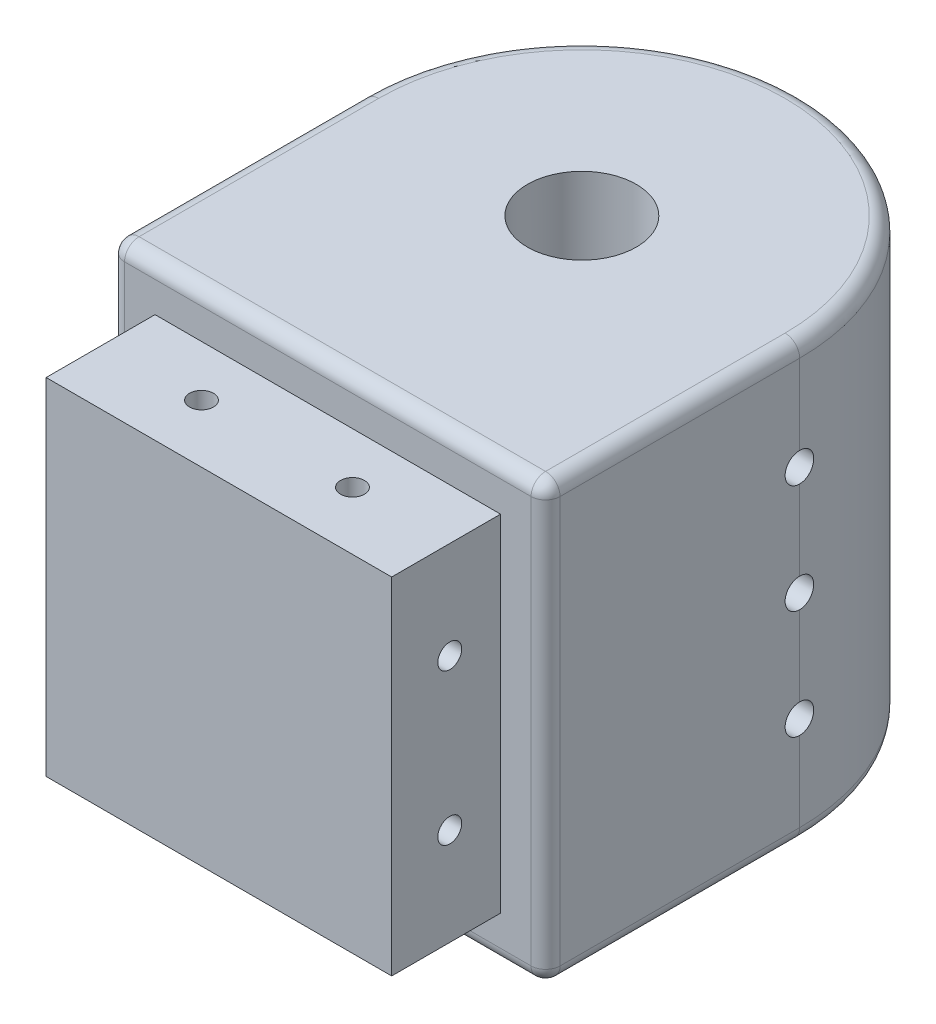
SolidWorks part; units mm, degrees
ref_plane "Front Plane" through (0, 0, 0) normal (0, 0, 1) x (1, 0, 0)
ref_plane "Top Plane" through (0, 0, 0) normal (0, 1, 0) x (1, 0, 0)
ref_plane "Right Plane" through (0, 0, 0) normal (1, 0, 0) x (0, 0, -1)
sketch "Sketch2" plane through (0, 0, 0) normal (0, 0, 1) x (1, 0, 0)
  line L1 (-30, -30) -> (30, -30)
  line L2 (-30, -30) -> (-30, 30)
  line L3 (-30, 30) -> (30, 30)
  line L4 (30, -30) -> (30, 30)
  line L5 (-30, -30) -> (30, 30) construction
  line L6 (-30, 30) -> (30, -30) construction
  point P0 (0, 0)
  dimension "D1" = 60
  dimension "D2" = 60
extrude "Boss-Extrude1" add sketch "Sketch2" along normal blind 80
sketch "Sketch3" plane through (0, 0, 80) normal (0, 0, 1) x (1, 0, 0)
  line L1 (-23.8, -23.8) -> (23.8, -23.8)
  line L2 (-23.8, -23.8) -> (-23.8, 23.8)
  line L3 (-23.8, 23.8) -> (23.8, 23.8)
  line L4 (23.8, -23.8) -> (23.8, 23.8)
  line L5 (-23.8, -23.8) -> (23.8, 23.8) construction
  line L6 (-23.8, 23.8) -> (23.8, -23.8) construction
  point P0 (0, 0)
  dimension "D1" = 47.6
  dimension "D2" = 47.6
extrude "Cut-Extrude1" cut sketch "Sketch3" against normal blind 15 flip side to cut
sketch "Sketch4" plane through (30, 0, 0) normal (1, 0, 0) x (0, 0, -1)
  line L0 (-65, 30) -> (-65, -30) construction
  line L1 (0, 30) -> (-60, 30)
  line L2 (0, 30) -> (0, 25)
  line L3 (0, 25) -> (-60, 25)
  line L4 (-60, 30) -> (-60, 25)
  line L5 (0, -30) -> (-60, -30)
  line L6 (0, -30) -> (0, -25)
  line L7 (0, -25) -> (-60, -25)
  line L8 (-60, -30) -> (-60, -25)
  dimension "D1" = 5
  dimension "D2" = 5
  dimension "D3" = 5
  dimension "D4" = 5
extrude "Cut-Extrude2" cut sketch "Sketch4" against normal blind 87
sketch "Sketch5" plane through (0, 25, 0) normal (0, 1, 0) x (1, 0, 0)
  circle A0 centre (0, -30) radius 7.5
  dimension "D2" = 15
  dimension "D1" = 30
extrude "Cut-Extrude3" cut sketch "Sketch5" against normal blind 87
sketch "Sketch7" plane through (0, 0, 0) normal (0, 0, -1) x (-1, 0, 0)
  line L5 (-30, 25) -> (30, 25) construction
  line L6 (-30, -30) -> (-15, -30)
  line L7 (-30, -30) -> (-30, 25)
  line L8 (-30, 25) -> (-15, 25)
  line L9 (-15, -30) -> (-15, 25)
  dimension "D1" = 15
extrude "Cut-Extrude4" [suppressed] cut sketch "Sketch7" against normal up to surface (60 mm away)
mirror "Mirror1" [suppressed] about plane through (0, 0, 0) normal (1, 0, 0)
fillet "Fillet1" [suppressed] radius 7
sketch "Sketch8" plane through (0, 25, 0) normal (0, 1, 0) x (1, 0, 0)
  line L1 (2.5, -34.5) -> (-2.5, -34.5)
  line L2 (2.5, -34.5) -> (2.5, -39.8)
  line L3 (2.5, -39.8) -> (-2.5, -39.8)
  line L4 (-2.5, -34.5) -> (-2.5, -39.8)
  circle A0 centre (0, -30) radius 7.5 construction
  dimension "D1" = 5.3
  dimension "D2" = 5
  dimension "D3" = 2.5
  dimension "D4" = 4.5
extrude "Cut-Extrude5" [suppressed] cut sketch "Sketch8" against normal through all
hole_wizard "M4 Tapped Hole1" positions "Sketch15" profile "Sketch16" tap size "M4" standard "ISO"
sketch "Sketch15" plane through (-23.8, 0, 0) normal (-1, 0, 0) x (0, 0, 1)
  point P0 (72, 10.4)
  point P2 (72, -10.4)
  dimension "D1" = 7
  dimension "D2" = 7
  dimension "D3" = 13.4
  dimension "D4" = 13.4
sketch "Sketch16" plane through (-23.8, 10.4, 72) normal (0, 1, 0) x (0, 0, 1)
  line L0 (0, 0) -> (0, 12.4914)
  line L1 (0, 12.4914) -> (1.65, 11.5)
  line L2 (1.65, 11.5) -> (1.65, 0)
  line L5 (1.65, 0) -> (0, 0)
  line L10 (0, 12.4914) -> (-1.65, 11.5) construction
  line L11 (0, -6.35) -> (0, 107.95) construction
  dimension "Tap Drill Dia." = 3.3
  dimension "Tap Drill Depth" = 11.5
  dimension "Drill Angle" = 118
cosmetic thread "Hole Thread1" parameters "D1"=8, "D2"=4
cosmetic thread "Hole Thread2" parameters "D1"=8, "D2"=4
sketch "Sketch18" plane through (0, 0, 0) normal (1, 0, 0) x (0, 0, -1)
  line L0 (0, 0) -> (-88.8317, 0) construction
pattern_circular "CirPattern1" count 4 every 90 about axis through (0, 0, 0) along (0, 0, 1) of "M4 Tapped Hole1"
fillet "Fillet2" radius 30 2 edges at (30, 0, 0) (-30, 0, 0)
sketch "Sketch19" plane through (30, 0, 0) normal (1, 0, 0) x (0, 0, -1)
  line L0 (-30, -25) -> (-30, 25) construction
  line L1 (-30, 20.6272) -> (-30, -19.2495) construction
  circle A0 centre (-30, 0) radius 2
  circle A1 centre (-30, 15) radius 2
  circle A2 centre (-30, -15) radius 2
  dimension "D1" = 4
  dimension "D2" = 15
  dimension "D3" = 15
extrude "Cut-Extrude6" cut sketch "Sketch19" against normal through all
ref_plane "Plane1" through (0, 0, 0) normal (0, 1, 0) x (1, 0, 0)
sketch "Sketch21" plane through (0, 25, 0) normal (0, 1, 0) x (1, 0, 0)
  line L3 (30, -60) -> (30, -30)
  line L4 (-30, -30) -> (-30, -60)
  line L5 (-30, -60) -> (30, -60)
  line L6 (30, -60) -> (30, -30)
  line L7 (-30, -30) -> (-30, -60)
  line L8 (-30, -60) -> (30, -60)
  circle A0 centre (0, -30) radius 7.5 construction
  circle A1 centre (0, -30) radius 7.5
  arc A2 (30, -30) -> (0, 0) centre (0, -30) ccw
  arc A3 (0, 0) -> (-30, -30) centre (0, -30) ccw
  arc A4 (30, -30) -> (0, 0) centre (0, -30) ccw
  arc A5 (0, 0) -> (-30, -30) centre (0, -30) ccw
  dimension "D1" = 0
extrude "Boss-Extrude3" add sketch "Sketch21" along normal blind 5
mirror "Mirror4" about plane through (0, 0, 0) normal (0, 1, 0) of "Boss-Extrude3"
fillet "Fillet3" radius 2 8 edges at (-30, 30, 47.5) (0, 30, 0) (-30, 0, 65) (0, -30, 65) (30, -30, 47.5) (30, 30, 47.5) (0, 30, 65) (30, 0, 65)
